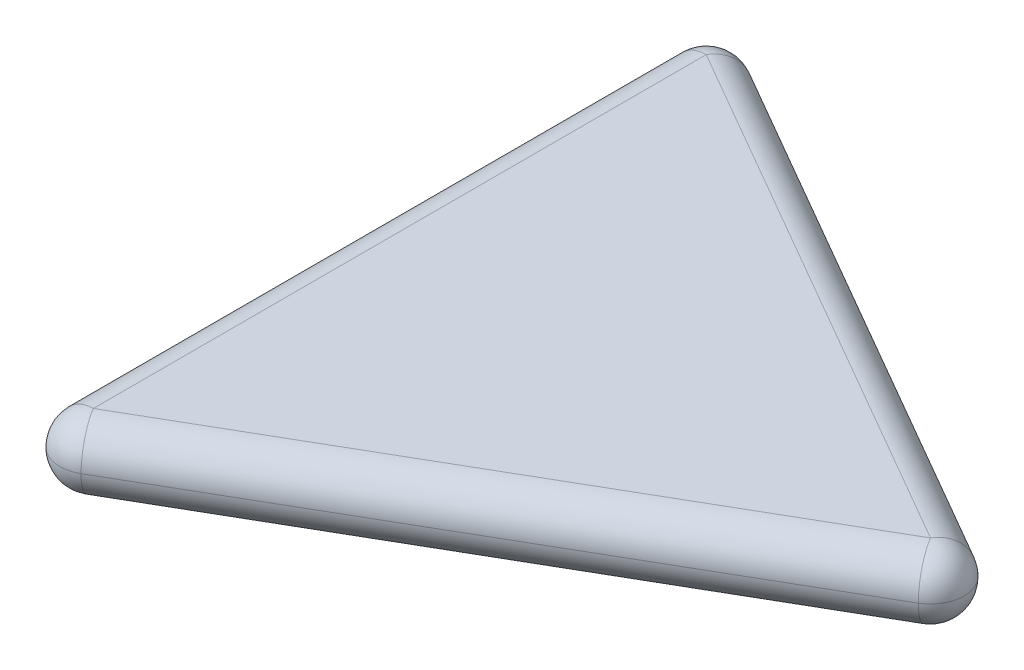
SolidWorks part; units mm, degrees
ref_plane "Front Plane" through (0, 0, 0) normal (0, 0, 1) x (1, 0, 0)
ref_plane "Top Plane" through (0, 0, 0) normal (0, 1, 0) x (1, 0, 0)
ref_plane "Right Plane" through (0, 0, 0) normal (1, 0, 0) x (0, 0, -1)
sketch "Sketch1" plane through (0, 0, 0) normal (0, 1, 0) x (1, 0, 0)
  line L1 (220.94, 17.3205) -> (-95.47, 199.9999)
  line L2 (-125.47, 182.6794) -> (-125.47, -182.6794)
  line L3 (-95.47, -199.9999) -> (220.94, -17.3205)
  circle A0 centre (250.94, 0) radius 0.0001
  circle A1 centre (0, 0) radius 125.47 construction
  arc A2 (-95.47, 199.9999) -> (-125.47, 182.6794) centre (-105.47, 182.6794) ccw
  arc A3 (-95.47, -199.9999) -> (-125.47, -182.6794) centre (-105.47, -182.6794) cw
  arc A4 (220.94, -17.3205) -> (220.94, 17.3205) centre (210.94, 0) ccw
  point P0 (250.94, 0)
  point P1 (-125.47, 217.321)
  point P2 (-115.47, -200)
  dimension "D1" = 20
  dimension "D2" = 20
  dimension "D3" = 20
extrude "Boss-Extrude1" add sketch "Sketch1" along normal blind 20 and the other way blind 20
fillet "Fillet1" radius 20 12 edges at (-125.47, -20, 0) (-115.47, -20, 199.9999) (62.735, -20, 108.6602) (230.94, -20, 0) (62.735, -20, -108.6602) (-115.47, -20, -199.9999) (-115.47, 20, -199.9999) (62.735, 20, -108.6602) (230.94, 20, 0) (62.735, 20, 108.6602) (-115.47, 20, 199.9999) (-125.47, 20, 0)
delete or keep bodies "Body-Delete1" type delete bodies bodies 101
